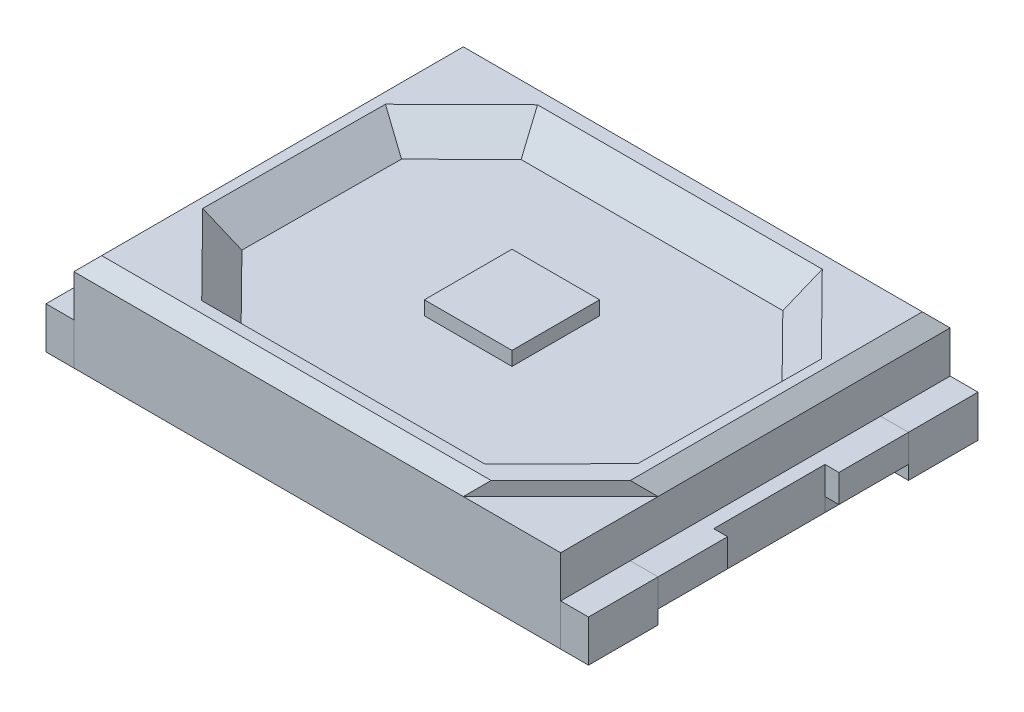
SolidWorks part; units mm, degrees
ref_plane "Front Plane" through (0, 0, 0) normal (0, 0, 1) x (1, 0, 0)
ref_plane "Top Plane" through (0, 0, 0) normal (0, 1, 0) x (1, 0, 0)
ref_plane "Right Plane" through (0, 0, 0) normal (1, 0, 0) x (0, 0, -1)
sketch "Sketch8" plane through (0, 0, 0) normal (0, 1, 0) x (1, 0, 0)
  line L0 (-1.0224, 1.2059) -> (1.0247, 1.2059)
  line L5 (-1.75, 1.4) -> (1.75, 1.4)
  line L6 (-1.75, 1.4) -> (-1.75, -1.4)
  line L7 (-1.75, -1.4) -> (1.75, -1.4)
  line L8 (1.75, 1.4) -> (1.75, -1.4)
  line L9 (-1.75, 1.4) -> (1.75, -1.4) construction
  line L10 (-1.75, -1.4) -> (1.75, 1.4) construction
  line L11 (-1.5804, -0.6433) -> (-1.0102, -1.2206)
  line L14 (1.5724, -0.6678) -> (1.5804, 0.6433)
  line L15 (1.5804, 0.6433) -> (1.0247, 1.2059)
  line L17 (-1.0224, 1.2059) -> (-1.5724, 0.6626)
  line L18 (-1.5724, 0.6626) -> (-1.5804, -0.6433)
  line L19 (-1.0102, -1.2206) -> (1.0247, -1.2206)
  line L20 (1.0247, -1.2206) -> (1.5724, -0.6678)
  line L21 (-0.6642, -1.5724) -> (0.6448, -1.5804) [skipped]
  line L22 (0.6642, 1.5724) -> (-0.6448, 1.5804) [skipped]
  line L24 (0.6422, -1.5815) -> (0.8286, -1.3973) [skipped]
  point P0 (0, 0)
  point P9 (0, 0)
  point P10 (0, 0)
  point P13 (1.086, 1.1325)
  point P14 (1.086, -1.157)
  point P18 (-1.0224, 1.2059)
  point P19 (1.0247, -1.2206)
  dimension "D1" = 3.5
  dimension "D2" = 2.8
extrude "Boss-Extrude3" add sketch "Sketch8" against normal blind 0.7 contours L6 L5 L8 L7
sketch "Sketch9" plane through (0, 0, 0) normal (0, 1, 0) x (1, 0, 0)
  line L0 (-1.0224, 1.2059) -> (-1.5724, 0.6626) construction
  line L1 (-1.5724, 0.6626) -> (-1.5804, -0.6433) construction
  line L2 (-1.5804, -0.6433) -> (-1.0102, -1.2206) construction
  line L3 (-1.0102, -1.2206) -> (1.0247, -1.2206) construction
  line L12 (1.0247, -1.2206) -> (1.5724, -0.6678) construction
  line L13 (1.5724, -0.6678) -> (1.5804, 0.6433) construction
  line L14 (1.5804, 0.6433) -> (1.0247, 1.2059) construction
  line L15 (-1.0224, 1.2059) -> (1.0247, 1.2059) construction
  line L16 (-1.0224, 1.2059) -> (-1.5724, 0.6626)
  line L17 (-1.5724, 0.6626) -> (-1.5804, -0.6433)
  line L18 (-1.5804, -0.6433) -> (-1.0102, -1.2206)
  line L19 (-1.0102, -1.2206) -> (1.0247, -1.2206)
  line L20 (1.0247, -1.2206) -> (1.5724, -0.6678)
  line L21 (1.5724, -0.6678) -> (1.5804, 0.6433)
  line L22 (1.5804, 0.6433) -> (1.0247, 1.2059)
  line L23 (-1.0224, 1.2059) -> (1.0247, 1.2059)
extrude "Cut-Extrude2" cut sketch "Sketch9" against normal blind 0.2
chamfer "Chamfer1" distance 0.1 angle 45 4 edges at (-1.75, 0, 0) (0, 0, -1.4) (1.75, 0, 0) (0, 0, 1.4)
sketch "Sketch10" plane through (0, 0, 0) normal (0, 1, 0) x (1, 0, 0)
  line L0 (1.75, -0.7) -> (1.05, -1.4)
  line L1 (1.75, 1.4) -> (1.75, -1.4) construction
  line L2 (-1.75, -1.4) -> (1.75, -1.4) construction
  line L3 (1.05, -1.4) -> (1.75, -1.4)
  line L4 (1.75, -1.4) -> (1.75, -0.7)
  line L6 (1.75, -1.4) -> (1.65, -1.3) construction
  line L7 (1.75, -1.4) -> (-1.75, -1.4) construction
  point P6 (0, 0)
  point P9 (0, 0)
  point P10 (0, 0)
  point P11 (1.75, -1.4)
  dimension "D1" = 0.7
extrude "Cut-Extrude3" cut sketch "Sketch10" against normal blind 0.1 contours L3 L4 L0
sketch "Sketch12" plane through (0, -0.7, 0) normal (0, -1, 0) x (1, 0, 0)
  line L0 (0, 0) -> (-0.4094, 0) construction
  line L1 (-1.75, -1.4) -> (-1.9501, -1.4)
  line L2 (-1.75, -1.4) -> (-1.75, -0.9)
  line L3 (-1.75, -0.9) -> (-1.9501, -0.9)
  line L4 (-1.9501, -1.4) -> (-1.9501, -0.9)
  line L5 (-0.4094, 0) -> (0, 0) construction
  line L6 (0, 0) -> (0, -0.3377) construction
  line L7 (-1.75, 0.9) -> (-1.9501, 0.9)
  line L8 (-1.9501, 1.4) -> (-1.9501, 0.9)
  line L9 (-1.75, 1.4) -> (-1.9501, 1.4)
  line L10 (-1.75, 1.4) -> (-1.75, 0.9)
  line L11 (1.75, 1.4) -> (1.75, 0.9)
  line L12 (1.75, 1.4) -> (1.9501, 1.4)
  line L13 (1.9501, 1.4) -> (1.9501, 0.9)
  line L14 (1.75, 0.9) -> (1.9501, 0.9)
  line L15 (1.75, -0.9) -> (1.9501, -0.9)
  line L16 (1.9501, -1.4) -> (1.9501, -0.9)
  line L17 (1.75, -1.4) -> (1.9501, -1.4)
  line L18 (1.75, -1.4) -> (1.75, -0.9)
  dimension "D1" = 0.5
  dimension "D2" = 0.2001
extrude "Boss-Extrude4" add sketch "Sketch12" against normal blind 0.3 separate body
sketch "Sketch13" plane through (0, -0.7, 0) normal (0, -1, 0) x (1, 0, 0)
  line L0 (1.75, -1.4) -> (1.75, 1.4) construction
  line L1 (1.9501, 0.9) -> (1.75, 0.9)
  line L2 (1.9501, 0.9) -> (1.9501, 0.4)
  line L3 (1.9501, 0.4) -> (1.85, 0.4)
  line L4 (1.75, 0.9) -> (1.75, 0.4)
  line L5 (0, 0) -> (0, 0.1702) construction
  line L6 (0, 0) -> (0.1265, 0) construction
  line L9 (1.75, -0.4) -> (1.75, 0.4)
  line L11 (1.85, -0.4) -> (1.85, 0.4)
  line L12 (1.9501, -0.4) -> (1.85, -0.4)
  line L13 (1.75, -0.9) -> (1.75, -0.4)
  line L14 (1.9501, -0.9) -> (1.75, -0.9)
  line L15 (1.9501, -0.9) -> (1.9501, -0.4)
  line L16 (-1.75, -0.9) -> (-1.75, -0.4)
  line L17 (-1.9501, -0.9) -> (-1.75, -0.9)
  line L18 (-1.9501, -0.9) -> (-1.9501, -0.4)
  line L19 (-1.9501, -0.4) -> (-1.85, -0.4)
  line L20 (-1.85, -0.4) -> (-1.85, 0.4)
  line L21 (-1.9501, 0.4) -> (-1.85, 0.4)
  line L22 (-1.9501, 0.9) -> (-1.9501, 0.4)
  line L23 (-1.9501, 0.9) -> (-1.75, 0.9)
  line L24 (-1.75, 0.9) -> (-1.75, 0.4)
  line L25 (-1.75, -0.4) -> (-1.75, 0.4)
  dimension "D1" = 0.5
  dimension "D2" = 0.1
extrude "Boss-Extrude8" add sketch "Sketch13" against normal blind 0.3 separate body contours L16 L25 L24 L23 L22 L21 L20 L19 L18 L17 | L9 L4 L1 L2 L3 L11 L12 L15 L14 L13
sketch "Sketch15" plane through (0, -0.7, 0) normal (0, -1, 0) x (1, 0, 0)
  line L0 (-1.9501, -0.9) -> (-1.9501, -0.4) construction
  line L1 (1.75, -1.4) -> (1.75, 1.4) construction
  line L6 (1.75, 0.9) -> (1.75, -0.9) construction
  line L7 (1.75, 0.9) -> (0.7598, 0.9)
  line L8 (1.75, 0.9) -> (1.75, 0.2676)
  line L11 (0.7598, -0.9) -> (1.75, -0.9)
  line L14 (1.75, -0.9) -> (1.75, -0.2676)
  line L15 (-0.1175, 0.4652) -> (0.325, 0.4652)
  line L16 (-0.2175, 0.3652) -> (-0.2175, -0.3652)
  line L17 (-0.1175, -0.4652) -> (0.325, -0.4652)
  line L18 (1.75, 0.2676) -> (1.75, -0.2676)
  line L19 (-0.2175, 0) -> (1.75, 0) construction
  line L20 (-1.75, 1.4) -> (1.75, 1.4) construction
  line L21 (-1.75, -1.4) -> (1.75, -1.4) construction
  line L22 (-1.75, 0.9) -> (-1.3929, 0.9)
  line L23 (-1.75, 0.9) -> (-1.75, -0.9)
  line L24 (-1.75, -0.9) -> (-1.3929, -0.9)
  line L26 (-0.9937, 0.4652) -> (-0.9264, 0.4652)
  line L29 (-0.8264, 0.3652) -> (-0.8264, -0.2652)
  line L30 (-0.9937, -0.3652) -> (-0.9264, -0.3652)
  line L31 (-1.3929, -0.8) -> (-1.3929, -0.9)
  line L32 (-1.75, -1.4) -> (-1.75, 1.4) construction
  line L33 (-0.8264, -1.3895) -> (-0.2264, -1.3895)
  line L34 (-0.8264, -1.3895) -> (-0.8264, -0.6657)
  line L35 (-0.8264, -0.6657) -> (-0.2264, -0.6657)
  line L36 (-0.2264, -1.3895) -> (-0.2264, -0.6657)
  line L37 (-1.85, 0) -> (-1.7881, 0) construction
  line L38 (-1.85, -0.4) -> (-1.85, 0.4) construction
  line L39 (-0.8264, 0.6657) -> (-0.2264, 0.6657)
  line L40 (-0.2264, 1.3895) -> (-0.2264, 0.6657)
  line L41 (-0.8264, 1.3895) -> (-0.2264, 1.3895)
  line L42 (-0.8264, 1.3895) -> (-0.8264, 0.6657)
  arc A0 (0.7598, 0.9) -> (0.325, 0.4652) centre (0.325, 0.9) cw
  arc A1 (0.7598, -0.9) -> (0.325, -0.4652) centre (0.325, -0.9) ccw
  arc A2 (-0.2175, -0.3652) -> (-0.1175, -0.4652) centre (-0.1175, -0.3652) ccw
  arc A3 (-0.1175, 0.4652) -> (-0.2175, 0.3652) centre (-0.1175, 0.3652) ccw
  arc A4 (-1.3929, 0.9) -> (-0.9192, 0.4652) centre (-0.9565, 0.9) ccw
  arc A5 (-1.3929, -0.8) -> (-0.9192, -0.3652) centre (-0.9565, -0.8) cw
  arc A6 (-0.9264, -0.3652) -> (-0.8264, -0.2652) centre (-0.9264, -0.2652) ccw
  arc A7 (-0.9264, 0.4652) -> (-0.8264, 0.3652) centre (-0.9264, 0.3652) cw
  circle A8 centre (-0.5264, -1.0276) radius 0.2368
  circle A9 centre (-0.5264, 1.0276) radius 0.2368
  point P45 (-0.8264, -0.3652)
  point P48 (-0.8264, 0.4652)
  point P68 (-1.7881, 0)
  point P69 (-0.8264, -1.4)
  point P70 (-0.8264, -1.4)
  point P71 (-0.8264, -1.3895)
  line M36 (1.75, 1.4) -> (-1.75, 1.4)
  line M37 (-1.75, 1.4) -> (-1.75, -1.4)
  line M38 (-1.75, -1.4) -> (1.75, -1.4)
  line M39 (1.75, -1.4) -> (1.75, 1.4)
  dimension "D1" = 0.1
  dimension "D3" = 1.425
  dimension "D5" = 0.7935
  dimension "D6" = 0.9236
  dimension "D8" = 0.7237
  dimension "D10" = 0.5
  dimension "D11" = 0.3619
  dimension "D12" = 0.4736
  dimension "D13" = 0.3
  dimension "D15" = 0.4364
  dimension "D16" = 0.6
  dimension "D17" = 0.9936
  dimension "D18" = 0.4364
  dimension "D19" = 0.8236
  dimension "D20" = 1.1348
  dimension "D21" = 1.0348
  dimension "D2" = 0.7303
  dimension "D4" = 0.6
  dimension "D7" = 1.8
  dimension "D9" = 0.9236
  dimension "D14" = 1.9675
  dimension "D22" = 0.0105
extrude "Cut-Extrude12" cut sketch "Sketch15" against normal blind 0.1 contours L15 A3 L16 A2 L17 A1 L11 L7 A0 M39 | A7 A4 L22 L24 L31 A5 A6 L29 M37 | L42 L39 L40 A9 M36 | L36 L35 L34 A8 M38 region at (0.9167, -0.7, 0) region at (-1.3729, -0.7, 0.023) region at (-0.817, -0.7, -1.0276) region at (-0.817, -0.7, 1.0276)
chamfer "Chamfer5" distance 0.2 angle 45 8 edges at (1.3025, -0.2, -0.9246) (1.5764, -0.2, 0.0122) (1.2985, -0.2, 0.9442) (0.0072, -0.2, 1.2206) (-1.2953, -0.2, 0.9319) (-1.5764, -0.2, -0.0097) (-1.2974, -0.2, -0.9343) (0.0011, -0.2, -1.2059)
sketch "Sketch25" plane through (0, -0.2, 0) normal (0, 1, 0) x (1, 0, 0)
  line L1 (-0.315, -0.315) -> (0.315, -0.315)
  line L2 (-0.315, -0.315) -> (-0.315, 0.315)
  line L3 (-0.315, 0.315) -> (0.315, 0.315)
  line L4 (0.315, -0.315) -> (0.315, 0.315)
  line L5 (-0.315, -0.315) -> (0.315, 0.315) construction
  line L6 (-0.315, 0.315) -> (0.315, -0.315) construction
  point P0 (0, 0)
  dimension "D1" = 0.63
  dimension "D2" = 0.63
extrude "Boss-Extrude13" add sketch "Sketch25" along normal blind 0.1 contours L2 L1 L4 L3
sketch "Sketch27" plane through (1.9501, 0, 0) normal (1, 0, 0) x (0, 0, -1)
  line L0 (0.9, -0.7) -> (0.4, -0.7) construction
  line L1 (0.4, -0.7) -> (0.9, -0.7)
  line L2 (0.4, -0.7) -> (0.4, -0.6)
  line L3 (0.4, -0.6) -> (0.9, -0.6)
  line L4 (0.9, -0.7) -> (0.9, -0.6)
  line L5 (0.9, -0.4) -> (0.9, -0.7) construction
  dimension "D1" = 0.1
  dimension "D2" = 0.5
extrude "Cut-Extrude25" cut sketch "Sketch27" against normal blind 0.1
sketch "Sketch30" plane through (1.9501, 0, 0) normal (1, 0, 0) x (0, 0, -1)
  line L0 (-0.4, -0.4) -> (-0.4, -0.7) construction
  line L1 (-0.9, -0.7) -> (-0.4, -0.7)
  line L2 (-0.9, -0.7) -> (-0.9, -0.6)
  line L3 (-0.9, -0.6) -> (-0.4, -0.6)
  line L4 (-0.4, -0.7) -> (-0.4, -0.6)
  dimension "D1" = 0.1
extrude "Cut-Extrude26" cut sketch "Sketch30" against normal blind 0.1 contours L2 L1 L4 L3
sketch "Sketch31" plane through (-1.9501, 0, 0) normal (-1, 0, 0) x (0, 0, 1)
  line L0 (-0.4, -0.4) -> (-0.4, -0.7) construction
  line L1 (-0.9, -0.7) -> (-0.4, -0.7)
  line L2 (-0.9, -0.7) -> (-0.9, -0.6)
  line L3 (-0.9, -0.6) -> (-0.4, -0.6)
  line L4 (-0.4, -0.7) -> (-0.4, -0.6)
  dimension "D1" = 0.1
extrude "Cut-Extrude27" cut sketch "Sketch31" against normal blind 0.1
sketch "Sketch32" plane through (-1.9501, 0, 0) normal (-1, 0, 0) x (0, 0, 1)
  line L0 (0.9, -0.4) -> (0.9, -0.7) construction
  line L1 (0.4, -0.7) -> (0.9, -0.7)
  line L2 (0.4, -0.7) -> (0.4, -0.6)
  line L3 (0.4, -0.6) -> (0.9, -0.6)
  line L4 (0.9, -0.7) -> (0.9, -0.6)
  dimension "D1" = 0.1
extrude "Cut-Extrude28" cut sketch "Sketch32" against normal blind 0.1
